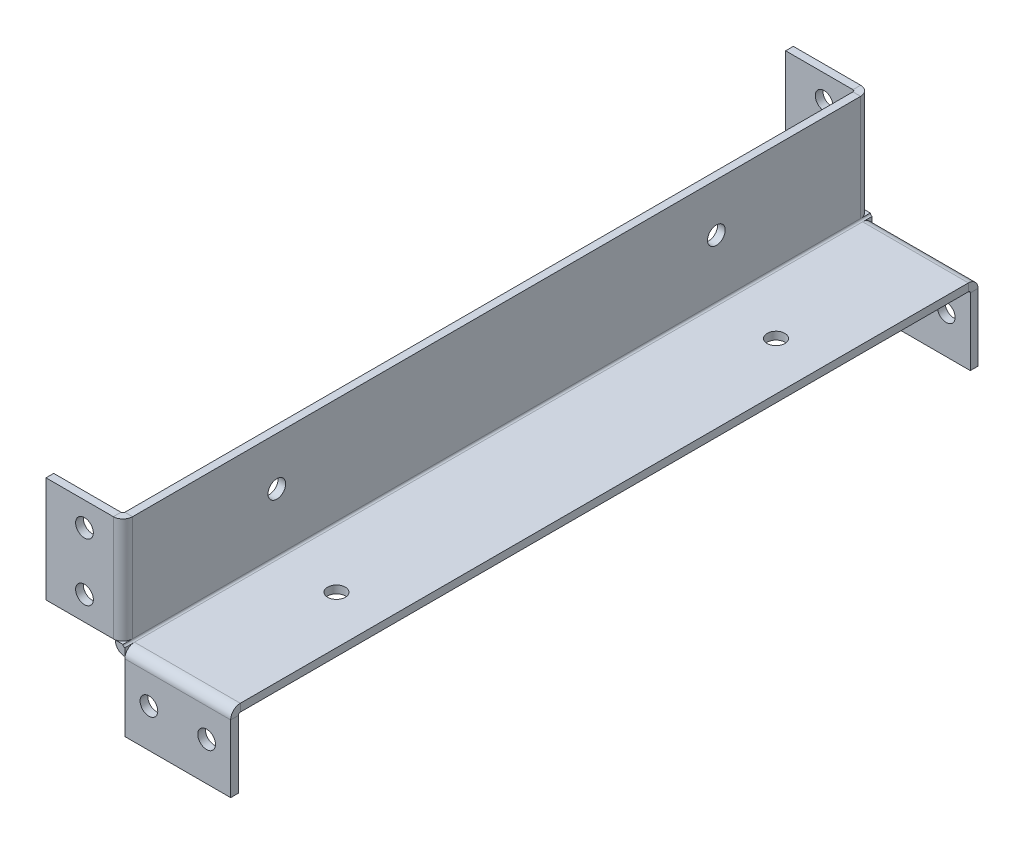
SolidWorks part; units mm, degrees
note: The reader was unsure of these and kept them because the rebuilt part matched: flange length of "Edge-Flange1", "Edge-Flange2".
ref_plane "Front Plane" through (0, 0, 0) normal (0, 0, 1) x (1, 0, 0)
ref_plane "Top Plane" through (0, 0, 0) normal (0, 1, 0) x (1, 0, 0)
ref_plane "Right Plane" through (0, 0, 0) normal (1, 0, 0) x (0, 0, -1)
sketch "Sketch1" plane through (0, 0, 0) normal (0, 1, 0) x (1, 0, 0)
  line L1 (30, 194.25) -> (-30, 194.25)
  line L2 (30, 194.25) -> (30, -194.25)
  line L3 (30, -194.25) -> (-30, -194.25)
  line L4 (-30, 194.25) -> (-30, -194.25)
  line L5 (30, 194.25) -> (-30, -194.25) construction
  line L6 (30, -194.25) -> (-30, 194.25) construction
  point P0 (0, 0)
  dimension "D1" = 60
  dimension "D2" = 388.5
sheet metal parameters "Sheet-Metal1" thickness 4 parameters "D1"=1
base flange "Base-Flange1" sketch "Sketch1" thickness 4 reverse thickness direction yes parameters "D1"=1
edge flange "Edge-Flange1" sketch "Sketch5" flange angle 90 flange length 60 flange position material inside bend radius 1 thickness 4 parameters "D6"=10
sketch "Sketch5" plane through (-30, 4, 0) normal (-1, 0, 0) x (0, 0, 1)
  line L2 (-194.25, 0) -> (-194.25, 56)
  line L3 (-194.25, 56) -> (194.25, 56)
  line L4 (194.25, 56) -> (194.25, 0)
  line L5 (-194.25, 0) -> (194.25, 0) construction
  line L6 (-194.25, 0) -> (194.25, 0)
bend "EdgeBend1" bend radius 1 bend angle 90 parameters "D5"=1
edge flange "Edge-Flange2" sketch "Sketch14" flange profiles "Sketch14", "Sketch15", "Sketch16", "Sketch17" flange angle 90 flange length 40 flange position material inside bend radius 1 thickness 4 relief none parameters "D6"=10, "D8"=0.5
sketch "Sketch14" plane through (-30, 0, 194.25) normal (0, 0, -1) x (0, -1, 0)
  line L1 (-5, 0) -> (-60, 0) construction
  line L2 (-60, 0) -> (-60, 36)
  line L3 (-60, 36) -> (-5, 36)
  line L4 (-5, 36) -> (-5, 0)
  line L5 (-5, 0) -> (-60, 0)
sketch "Sketch15" plane through (0, 0, 194.25) normal (0, 0, -1) x (1, 0, 0)
  line L0 (30, 0) -> (-25, 0) construction
  line L1 (30, 0) -> (-25, 0)
  line L2 (30, 0) -> (30, 36)
  line L3 (30, 36) -> (-25, 36)
  line L4 (-25, 36) -> (-25, 0)
sketch "Sketch16" plane through (-30, 0, -194.25) normal (0, 0, 1) x (0, 1, 0)
  line L0 (60, 0) -> (5, 0) construction
  line L1 (60, 0) -> (5, 0)
  line L2 (60, 0) -> (60, 36)
  line L3 (60, 36) -> (5, 36)
  line L4 (5, 36) -> (5, 0)
sketch "Sketch17" plane through (0, 0, -194.25) normal (0, 0, 1) x (-1, 0, 0)
  line L0 (25, 0) -> (-30, 0) construction
  line L1 (25, 0) -> (-30, 0)
  line L2 (25, 0) -> (25, 36)
  line L3 (25, 36) -> (-30, 36)
  line L4 (-30, 36) -> (-30, 0)
bend "EdgeBend2" bend radius 1 bend angle 90 parameters "D5"=2
bend "EdgeBend3" bend radius 1 bend angle 90 parameters "D5"=3
bend "EdgeBend4" bend radius 1 bend angle 90 parameters "D5"=4
bend "EdgeBend5" bend radius 1 bend angle 90 parameters "D5"=5
sketch "Sketch18" plane through (0, 0, 194.25) normal (0, 0, 1) x (1, 0, 0)
  line L0 (-25, 4) -> (30, 4) construction
  line L1 (-26, 60) -> (-26, 5) construction
  line L2 (-66, 60) -> (-31, 60) construction
  line L3 (30, -1) -> (30, -36) construction
  circle A0 centre (-46, 47.5) radius 4.6
  circle A1 centre (-46, 17.5) radius 4.6
  circle A2 centre (-12.5, -16) radius 4.6
  circle A3 centre (17.5, -16) radius 4.6
  dimension "D7" = 9.2
  dimension "D1" = 30
  dimension "D2" = 30
  dimension "D3" = 20
  dimension "D4" = 20
  dimension "D5" = 12.5
  dimension "D6" = 12.5
extrude "Extrude1" cut sketch "Sketch18" against normal through all normal cut yes
sketch "Sketch19" plane through (-26, 0, 0) normal (1, 0, 0) x (0, 0, -1)
  line L0 (-189.25, 60) -> (189.25, 60) construction
  line L1 (-194.25, 5) -> (-194.25, 60) construction
  line L2 (194.25, 5) -> (194.25, 60) construction
  circle A0 centre (-114.25, 35) radius 4.6
  circle A1 centre (114.25, 35) radius 4.6
  dimension "D4" = 9.2
  dimension "D1" = 25
  dimension "D2" = 80
  dimension "D3" = 80
extrude "Extrude2" cut sketch "Sketch19" against normal blind 4 normal cut yes
sketch "Sketch20" plane through (0, 4, 0) normal (0, 1, 0) x (1, 0, 0)
  line L0 (30, -189.25) -> (30, 189.25) construction
  line L1 (-25, -194.25) -> (30, -194.25) construction
  line L2 (30, 194.25) -> (-25, 194.25) construction
  circle A0 centre (5, 114.25) radius 4.6
  circle A1 centre (5, -114.25) radius 4.6
  dimension "D2" = 9.2
  dimension "D1" = 25
  dimension "D3" = 80
  dimension "D4" = 80
extrude "Extrude3" cut sketch "Sketch20" against normal blind 4 normal cut yes
flat pattern "Flat-Pattern1" [suppressed]
sketch "Bend-Lines1" plane through (0, 4, 0) normal (0, 1, 0) x (-1, 0, 0)
  line L0 (25, -199.4012) -> (-30, -199.4012) construction
  line L1 (82.8023, -199.4012) -> (27.8023, -199.4012) construction
  line L2 (-30, 199.4012) -> (25, 199.4012) construction
  line L3 (27.8023, 199.4012) -> (82.8023, 199.4012) construction
  line L4 (26.4012, -203) -> (26.4012, 203) construction
  line L5 (25, -199.4012) -> (-30, -199.4012) construction
  line L6 (82.8023, -199.4012) -> (27.8023, -199.4012) construction
  line L7 (-30, 199.4012) -> (25, 199.4012) construction
  line L8 (27.8023, 199.4012) -> (82.8023, 199.4012) construction
  line L9 (26.4012, -203) -> (26.4012, 203) construction
sketch3d "Bounding-Box1" [suppressed]
  line L0 (52.8023, 32.8023, 0) -> (52.8023, -438.8023, 0) construction
  line L1 (-60, 32.8023, 0) -> (-60, -438.8023, 0) construction
  line L2 (52.8023, 32.8023, 0) -> (-60, 32.8023, 0) construction
  line L3 (52.8023, -438.8023, 0) -> (-60, -438.8023, 0) construction
bend of the flat pattern "Flatten-<EdgeBend1>1"
bend of the flat pattern "Flatten-<EdgeBend2>1"
bend of the flat pattern "Flatten-<EdgeBend3>1"
bend of the flat pattern "Flatten-<EdgeBend4>1"
bend of the flat pattern "Flatten-<EdgeBend5>1"
